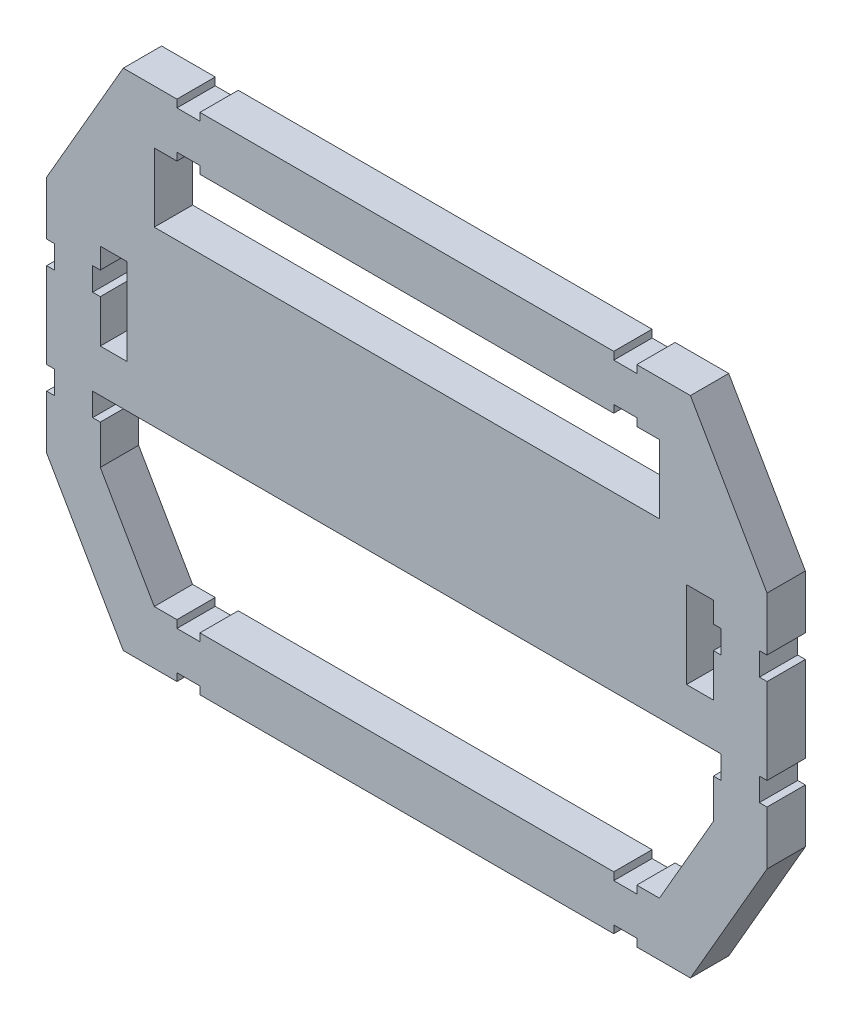
SolidWorks part; units mm, degrees
ref_plane "Plan de face" through (0, 0, 0) normal (0, 0, 1) x (1, 0, 0)
ref_plane "Plan de dessus" through (0, 0, 0) normal (0, 1, 0) x (1, 0, 0)
ref_plane "Plan de droite" through (0, 0, 0) normal (1, 0, 0) x (0, 0, -1)
sketch "Esquisse1" plane through (0, 0, 0) normal (0, 0, 1) x (1, 0, 0)
  line L0 (22, -30.0222) -> (-32, -30.0222)
  line L1 (-32, -30.0222) -> (-32, -29.0222)
  line L2 (-32, -29.0222) -> (-35, -29.0222)
  line L3 (-35, -29.0222) -> (-35, -30.0222)
  line L4 (-35, -30.0222) -> (-42, -30.0222)
  line L5 (-42, -30.0222) -> (-52, -12.7017)
  line L6 (-52, -12.7017) -> (-52, -5.7017)
  line L7 (-52, -5.7017) -> (-51, -5.7017)
  line L8 (-51, -5.7017) -> (-51, -2.7017)
  line L9 (-51, -2.7017) -> (-52, -2.7017)
  line L10 (-52, -2.7017) -> (-52, 8.4752)
  line L11 (-5, -30.0222) -> (-5, 35.7957) construction
  line L12 (35, 2.8868) -> (-45, 2.8868) construction
  line L13 (-47, -21.362) -> (-5, 2.8868) construction
  line L14 (-45, 8.4752) -> (-45, -2.7017)
  line L15 (-45, -2.7017) -> (-46, -2.7017)
  line L16 (-46, -2.7017) -> (-46, -5.7017)
  line L17 (-46, -5.7017) -> (-45, -5.7017)
  line L18 (-45, -5.7017) -> (-45, -10.8261)
  line L19 (-45, -10.8261) -> (-37.9585, -23.0222)
  line L20 (-37.9585, -23.0222) -> (-35, -23.0222)
  line L21 (-35, -23.0222) -> (-35, -24.0222)
  line L22 (-35, -24.0222) -> (-32, -24.0222)
  line L23 (-32, -24.0222) -> (-32, -23.0222)
  line L24 (-32, -23.0222) -> (22, -23.0222)
  line L25 (-47, 27.1355) -> (-5, 2.8868) construction
  line L26 (-32, 28.7957) -> (22, 28.7957)
  line L27 (-32, 29.7957) -> (-32, 28.7957)
  line L28 (-35, 29.7957) -> (-32, 29.7957)
  line L29 (-35, 28.7957) -> (-35, 29.7957)
  line L30 (-37.9585, 28.7957) -> (-35, 28.7957)
  line L31 (-37.9585, 28.7957) -> (-37.9585, 19.8426)
  line L32 (-37.9585, 19.8426) -> (27.9585, 19.8426)
  line L33 (-46, 11.4752) -> (-45, 11.4752)
  line L34 (-46, 8.4752) -> (-46, 11.4752)
  line L35 (-45, 8.4752) -> (-46, 8.4752)
  line L36 (-51, 8.4752) -> (-52, 8.4752)
  line L37 (-51, 11.4752) -> (-51, 8.4752)
  line L38 (-52, 11.4752) -> (-51, 11.4752)
  line L39 (-52, 18.4752) -> (-52, 11.4752)
  line L40 (-42, 35.7957) -> (-52, 18.4752)
  line L41 (-35, 35.7957) -> (-42, 35.7957)
  line L42 (-35, 34.7957) -> (-35, 35.7957)
  line L43 (-32, 34.7957) -> (-35, 34.7957)
  line L44 (-32, 35.7957) -> (-32, 34.7957)
  line L45 (22, 35.7957) -> (-32, 35.7957)
  line L46 (37, 27.1355) -> (-5, 2.8868) construction
  line L47 (37, -21.362) -> (-5, 2.8868) construction
  line L48 (22, 35.7957) -> (22, 34.7957)
  line L49 (22, 34.7957) -> (25, 34.7957)
  line L50 (25, 34.7957) -> (25, 35.7957)
  line L51 (25, 35.7957) -> (32, 35.7957)
  line L52 (32, 35.7957) -> (42, 18.4752)
  line L53 (42, 18.4752) -> (42, 11.4752)
  line L54 (42, 11.4752) -> (41, 11.4752)
  line L55 (41, 11.4752) -> (41, 8.4752)
  line L56 (41, 8.4752) -> (42, 8.4752)
  line L57 (35, 8.4752) -> (36, 8.4752)
  line L58 (36, 8.4752) -> (36, 11.4752)
  line L59 (36, 11.4752) -> (35, 11.4752)
  line L60 (27.9585, 19.8426) -> (27.9585, 28.7957)
  line L61 (35, -2.7017) -> (-45, -2.7017)
  line L62 (27.9585, 28.7957) -> (25, 28.7957)
  line L63 (25, 28.7957) -> (25, 29.7957)
  line L64 (25, 29.7957) -> (22, 29.7957)
  line L65 (22, 29.7957) -> (22, 28.7957)
  line L66 (22, -24.0222) -> (22, -23.0222)
  line L67 (25, -24.0222) -> (22, -24.0222)
  line L68 (25, -23.0222) -> (25, -24.0222)
  line L69 (27.9585, -23.0222) -> (25, -23.0222)
  line L70 (35, -10.8261) -> (27.9585, -23.0222)
  line L71 (35, -5.7017) -> (35, -10.8261)
  line L72 (36, -5.7017) -> (35, -5.7017)
  line L73 (36, -2.7017) -> (36, -5.7017)
  line L74 (35, -2.7017) -> (36, -2.7017)
  line L75 (35, 8.4752) -> (35, -2.7017)
  line L76 (42, -2.7017) -> (42, 8.4752)
  line L77 (41, -2.7017) -> (42, -2.7017)
  line L78 (41, -5.7017) -> (41, -2.7017)
  line L79 (42, -5.7017) -> (41, -5.7017)
  line L80 (42, -12.7017) -> (42, -5.7017)
  line L81 (32, -30.0222) -> (42, -12.7017)
  line L82 (25, -30.0222) -> (32, -30.0222)
  line L83 (25, -29.0222) -> (25, -30.0222)
  line L84 (22, -29.0222) -> (25, -29.0222)
  line L85 (22, -30.0222) -> (22, -29.0222)
  line L86 (35, 2.8868) -> (31.5, 2.8868)
  line L87 (31.5, 2.8868) -> (31.5, 14.1772)
  line L88 (31.5, 14.1772) -> (35, 14.1772)
  line L89 (35, 14.1772) -> (35, 11.4752)
  line L90 (35, 11.4752) -> (34.9646, 11.6959)
  line L91 (-45, 2.8868) -> (-41.5, 2.8868)
  line L92 (-41.5, 2.8868) -> (-41.5, 14.1772)
  line L93 (-41.5, 14.1772) -> (-45, 14.1772)
  line L94 (-45, 14.1772) -> (-45, 11.4752)
  point P10 (-47, -21.362)
  point P41 (-52, 2.8868)
  point P73 (-5, 28.7957)
  point P74 (-5, -23.0222)
  point P75 (-5, -23.0222)
  point P94 (42, 2.8868)
  dimension "D1" = 1
  dimension "D2" = 3
  dimension "D3" = 7
  dimension "D4" = 3
  dimension "D5" = 7
  dimension "D6" = 60
  dimension "D7" = 90
  dimension "D8" = 1
  dimension "D9" = 1
  dimension "D10" = 1
  dimension "D11" = 7
  dimension "D12" = 7
  dimension "D13" = 7
  dimension "D14" = 20
  dimension "D15" = 30
  dimension "D16" = 2.702
  dimension "D17" = 3.5
extrude "Boss.-Extru.1" add sketch "Esquisse1" along normal blind 5 contours L0 L85 L84 L83 L82 L81 L80 L79 L78 L77 L76 L56 L55 L54 L53 L52 L51 L50 L49 L48 L45 L44 L43 L42 L41 L40 L39 L38 L37 L36 L10 L9 L8 L7 L6 L5 L4 L3 L2 L1 L94 L93 L92 L91 L61 L86 L87 L88 region at (-5, 5.8534, 0)
